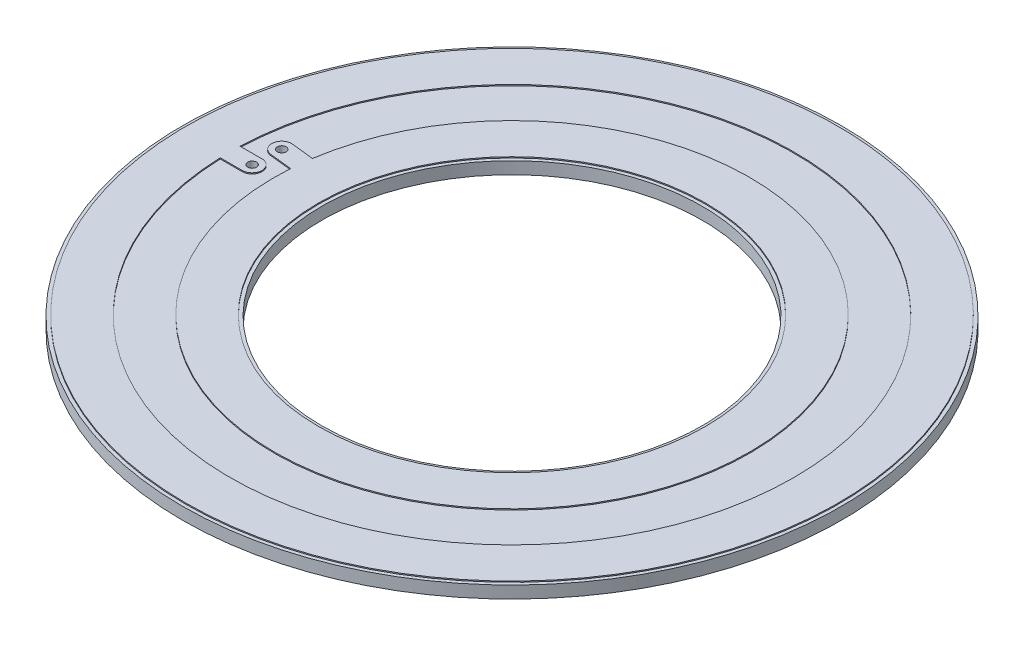
SolidWorks part; units mm, degrees
ref_plane "Спереди" through (0, 0, 0) normal (0, 0, 1) x (1, 0, 0)
ref_plane "Сверху" through (0, 0, 0) normal (0, 1, 0) x (1, 0, 0)
ref_plane "Справа" through (0, 0, 0) normal (1, 0, 0) x (0, 0, -1)
sketch "Эскиз1" plane through (0, 0, 0) normal (0, 1, 0) x (1, 0, 0)
  circle A0 centre (0, 0) radius 17.2
  circle A1 centre (0, 0) radius 29.8
  dimension "D1" = 34.4
  dimension "D2" = 59.6
extrude "Бобышка-Вытянуть1" add sketch "Эскиз1" along normal blind 1.1
sketch "Эскиз2" plane through (0, 1.1, 0) normal (0, 1, 0) x (1, 0, 0)
  circle A0 centre (0, 0) radius 29.5
  circle A1 centre (0, 0) radius 25.5
  circle A2 centre (0, 0) radius 21.5
  circle A3 centre (0, 0) radius 17.5
  circle A5 centre (0, 0) radius 17.2 construction
  circle A7 centre (0, 0) radius 29.8 construction
  dimension "D1" = 4
  dimension "D2" = 4
  dimension "D3" = 4
  dimension "D4" = 0.3
extrude "Бобышка-Вытянуть2" add sketch "Эскиз2" along normal blind 0.1 contours A2 A3 | A0 A1 region at (-28.6656, 1.1, 0) region at (-20.8919, 1.1, 0)
sketch "Эскиз4" plane through (0, 1.1, 0) normal (0, 1, 0) x (1, 0, 0)
  line L0 (0, 0) -> (-33.7363, 0) construction
  circle A0 centre (-23.5, 0) radius 0.4
  circle A1 centre (-23.3623, 2.54) radius 0.4
  circle A3 centre (0, 0) radius 23.5 construction
  circle A4 centre (0, 0) radius 21.5 construction
  dimension "D1" = 2
  dimension "D2" = 0.8
  dimension "D3" = 0.8
  dimension "D5" = 47
  dimension "D4" = 2.54
extrude "Вырез-Вытянуть1" cut sketch "Эскиз4" against normal through all
sketch "Эскиз5" plane through (0, 1.1, 0) normal (0, 1, 0) x (1, 0, 0)
  circle A0 centre (-23.3623, 2.54) radius 0.9
  circle A1 centre (-23.5, 0) radius 0.4 construction
  circle A3 centre (-23.5, 0) radius 0.9
  circle A4 centre (-23.5, 0) radius 0.4
  circle A5 centre (-23.3623, 2.54) radius 0.4 construction
  circle A6 centre (-23.3623, 2.54) radius 0.4
  dimension "D2" = 1.8
  dimension "D1" = 1.8
extrude "Бобышка-Вытянуть3" add sketch "Эскиз5" along normal blind 0.1
ref_axis "Ось1" through (0, 1.1, 0) along (0, -1, 0)
sketch "Эскиз6" plane through (0, 1.1, 0) normal (0, 1, 0) x (1, 0, 0)
  line L2 (-23.3623, 2.54) -> (0, 0) construction
  line L5 (-23.5, -0.9) -> (-27.4565, -0.9)
  line L6 (-23.5, 0.9) -> (-27.4565, 0.9)
  line L7 (-27.4565, 0.9) -> (-27.4565, -0.9)
  line L8 (-23.5, -0.9) -> (-24.1108, 0)
  line L9 (-24.1108, 0) -> (-23.5, 0.9)
  line L10 (-23.3623, 1.64) -> (-20.0181, 1.2764)
  line L11 (-20.0181, 1.2764) -> (-19.8247, 3.0554)
  line L12 (-23.1689, 3.419) -> (-19.8247, 3.0554)
  line L13 (-23.3623, 1.64) -> (-22.768, 2.4754)
  line L14 (-22.768, 2.4754) -> (-23.1689, 3.419)
  circle A0 centre (-23.3623, 2.54) radius 0.9 construction
  circle A19 centre (-23.5, 0) radius 0.9 construction
  circle A20 centre (-23.5, 0) radius 0.9 construction
  point P16 (-19.9214, 2.1659)
  point P18 (-24.1108, 0)
extrude "Бобышка-Вытянуть4" add sketch "Эскиз6" along normal blind 0.1
